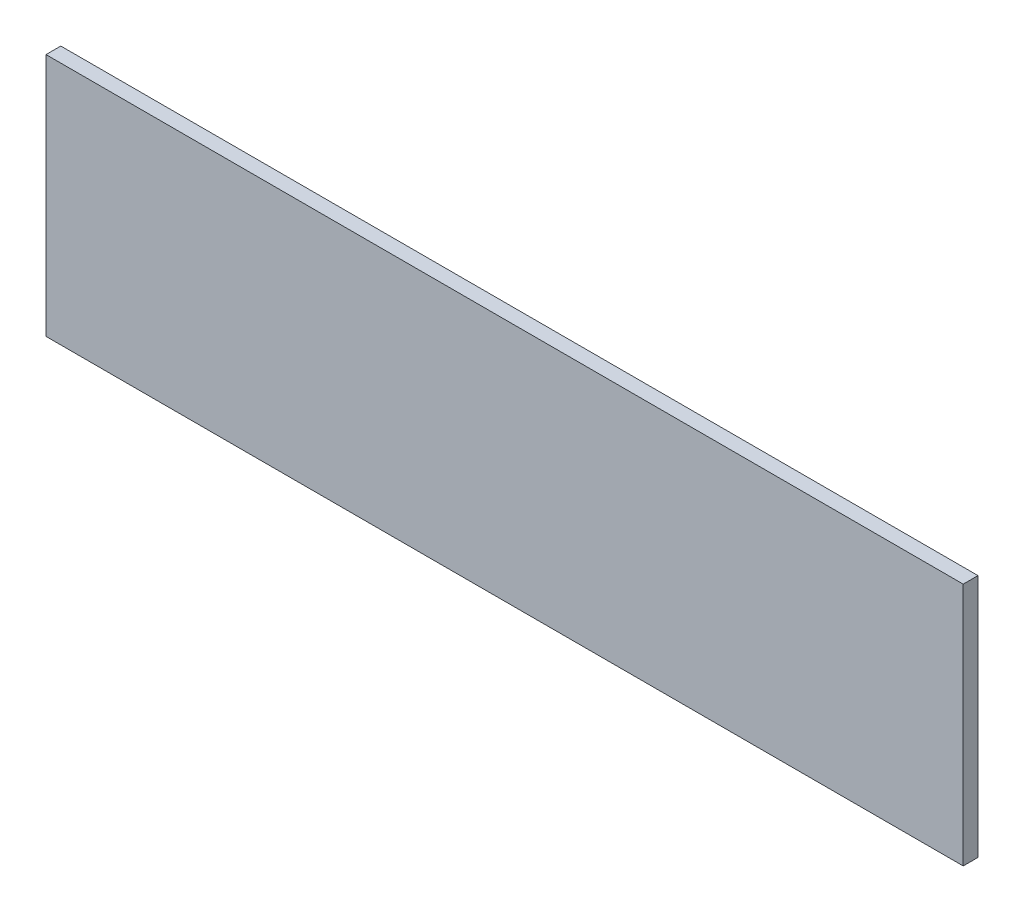
SolidWorks part; units mm, degrees
ref_plane "Front Plane" through (0, 0, 0) normal (0, 0, 1) x (1, 0, 0)
ref_plane "Top Plane" through (0, 0, 0) normal (0, 1, 0) x (1, 0, 0)
ref_plane "Right Plane" through (0, 0, 0) normal (1, 0, 0) x (0, 0, -1)
sketch "Sketch1" plane through (0, 0, 0) normal (0, 0, 1) x (1, 0, 0)
  line L2 (-62, -16.5) -> (62, -16.5)
  line L3 (-62, -16.5) -> (-62, 16.5)
  line L4 (-62, 16.5) -> (62, 16.5)
  line L5 (62, -16.5) -> (62, 16.5)
  line L6 (-62, -16.5) -> (62, 16.5) construction
  line L7 (-62, 16.5) -> (62, -16.5) construction
  point P2 (0, 0)
  dimension "D1" = 124
  dimension "D2" = 33
extrude "Boss-Extrude1" add sketch "Sketch1" along normal blind 2
